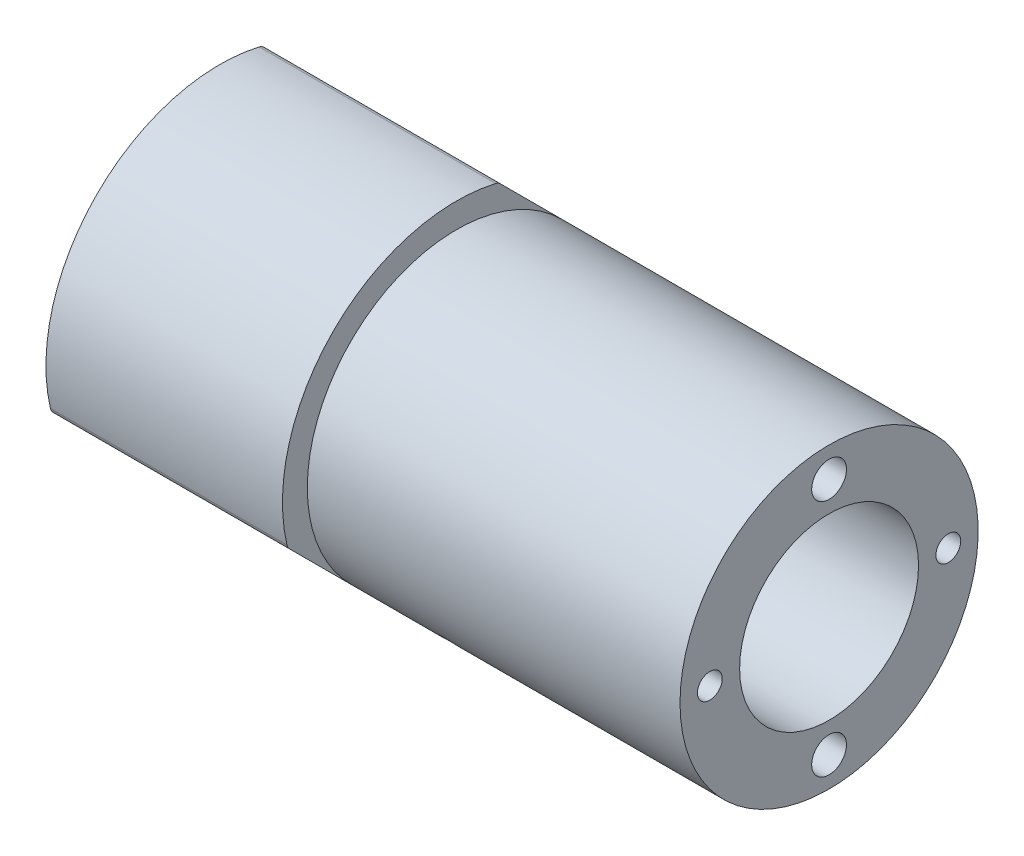
SolidWorks part; units mm, degrees
other "Markup1"
sketch "Sketch17" plane through (198.0015, -131.0823, 17.4914) normal (-0.589, 0.0933, 0.8027) x (0.8081, 0.0619, 0.5858)
sketch "Sketch19" plane through (198.0015, -131.0737, 17.5) normal (-0.589, 0.0933, 0.8027) x (0.8081, 0.0619, 0.5858)
material "AISI 304"
ref_plane "Front Plane" through (0, 0, 0) normal (0, 0, 1) x (1, 0, 0)
ref_plane "Top Plane" through (0, 0, 0) normal (0, 1, 0) x (1, 0, 0)
ref_plane "Right Plane" through (0, 0, 0) normal (1, 0, 0) x (0, 0, -1)
sketch "Sketch3" plane through (0, 0, 0) normal (0, 0, 1) x (1, 0, 0)
  line L0 (-58.5481, 189.9573) -> (284.033, 189.9573) construction
  line L2 (213.4012, -189.6279) -> (558.7345, -189.6279) construction
  line L4 (227.3705, -148.5737) -> (308.4812, -148.5737) construction
  line L25 (233.6593, -146.8737) -> (233.6593, -145.6737)
  line L26 (233.6593, -145.6737) -> (300.6593, -145.6737)
  line L27 (300.6593, -145.6737) -> (300.6593, -148.1737)
  line L28 (300.6593, -148.1737) -> (284.5593, -148.1737)
  line L29 (284.5593, -148.1737) -> (284.5593, -146.8713)
  line L30 (284.5593, -146.8713) -> (233.6593, -146.8737)
  line L31 (251.8003, -145.6737) -> (251.8003, -143.5284)
  line L32 (251.8003, -143.5284) -> (253.3698, -143.5284)
  line L33 (253.3698, -143.5284) -> (253.3698, -140.805)
  line L34 (253.3698, -140.805) -> (248.9846, -140.805)
  line L35 (248.9846, -140.805) -> (248.9846, -145.6737)
  line L36 (248.9846, -145.6737) -> (251.8003, -145.6737)
  line L38 (248.9846, -141.4136) -> (235.8861, -141.4136)
  line L39 (235.8861, -141.4136) -> (235.8861, -143.2479)
  line L40 (235.8861, -143.2479) -> (234.2244, -143.2479)
  line L41 (234.2244, -143.2479) -> (234.2244, -143.537)
  line L42 (234.2244, -143.537) -> (233.6702, -143.537)
  line L43 (233.6702, -143.537) -> (233.6702, -143.9524)
  line L44 (233.6702, -143.9524) -> (231.1317, -143.9524)
  line L45 (231.1317, -143.9524) -> (231.1317, -142.3308)
  line L46 (231.1317, -142.3308) -> (224.8078, -142.3308)
  line L47 (224.8078, -142.3308) -> (224.8078, -145.1987)
  line L48 (224.8078, -145.1987) -> (223.8385, -145.1987)
  line L49 (223.8385, -145.1987) -> (223.8385, -144.6096)
  line L50 (223.8385, -144.6096) -> (224.4112, -144.6096)
  line L51 (224.4112, -144.6096) -> (224.4112, -144.369)
  line L52 (224.4112, -144.369) -> (222.6328, -144.369)
  line L53 (222.6328, -144.369) -> (222.6328, -142.6667)
  line L54 (222.6328, -142.6667) -> (212.7719, -142.6667)
  line L55 (212.7719, -142.6667) -> (212.7719, -143.1416)
  line L56 (212.7719, -143.1416) -> (211.9894, -143.1416)
  line L57 (211.9894, -143.1416) -> (211.9894, -143.5179)
  line L58 (211.9894, -143.5179) -> (209.8233, -143.5179)
  line L59 (209.8233, -143.5179) -> (209.8233, -146.4993)
  line L60 (209.8233, -146.4993) -> (209.8233, -146.8823)
  line L61 (209.8233, -146.8823) -> (210.2598, -146.8823)
  line L62 (210.2598, -146.8823) -> (210.2598, -147.3433)
  line L63 (210.2598, -147.3433) -> (222.6328, -147.3433)
  line L64 (222.6328, -147.3433) -> (222.6328, -147.7892)
  line L65 (222.6328, -147.7892) -> (233.6593, -147.7892)
  line L66 (233.6593, -147.7892) -> (233.6593, -145.6737)
  line L67 (248.9846, -145.6737) -> (233.6593, -145.6737)
  line L68 (233.6593, -145.6737) -> (248.9846, -145.6737)
  line L69 (209.8233, -145.6737) -> (205.1515, -145.6737)
  line L70 (205.1515, -145.6737) -> (205.1515, -140.5737)
  line L71 (205.1515, -140.5737) -> (212.7719, -140.5737)
  line L72 (212.7719, -140.5737) -> (212.7719, -143.1416)
  line L73 (211.9894, -143.1416) -> (211.9894, -143.5179)
  line L74 (209.8233, -143.5179) -> (209.8233, -145.6737)
  line L75 (205.1515, -145.1987) -> (198.0015, -145.1987)
  line L83 (259.3015, -139.5737) -> (208.5515, -139.5737)
  line L84 (208.5515, -139.5737) -> (208.5515, -140.5737)
  line L85 (208.5515, -140.5737) -> (205.1515, -140.5737)
  line L86 (205.1515, -145.1987) -> (205.1515, -140.5737)
  line L87 (238.4273, -133.5737) -> (238.4273, -129.7144)
  line L88 (238.4273, -129.7144) -> (264.4415, -129.7144)
  line L89 (264.4415, -141.0573) -> (264.4415, -129.7144)
  line L90 (264.4415, -141.0573) -> (261.9375, -141.0573)
  line L91 (238.4273, -133.5737) -> (259.3015, -133.5737)
  line L92 (259.3015, -133.5737) -> (259.3015, -139.5737)
  line L93 (259.3015, -139.5737) -> (259.3015, -140.788)
  line L94 (259.3015, -140.788) -> (261.9375, -140.788)
  line L95 (250.6852, -139.5737) -> (250.6852, -140.805)
  line L96 (253.3698, -143.5284) -> (259.3015, -143.5284)
  line L97 (259.3015, -143.5284) -> (259.3015, -140.788)
  line L98 (259.3015, -143.5284) -> (302.0274, -143.5284)
  line L99 (302.0274, -143.5284) -> (302.0274, -145.1901)
  line L100 (302.0274, -145.1901) -> (304.5325, -145.1901)
  line L101 (304.5325, -145.1901) -> (304.5325, -141.0573)
  line L102 (304.5325, -141.0573) -> (264.4415, -141.0573)
  line L103 (238.4273, -133.5737) -> (221.8015, -133.5737)
  line L104 (161.2028, -147.3433) -> (161.2028, -146.4993)
  line L105 (161.2028, -146.4993) -> (209.8233, -146.4993)
  line L106 (209.8233, -146.8823) -> (210.2598, -146.8823)
  line L107 (210.2598, -147.3433) -> (222.6328, -147.3433)
  line L108 (210.2598, -147.3433) -> (161.2028, -147.3433)
  line L109 (209.8233, -146.4993) -> (209.8233, -146.8823)
  line L110 (209.8233, -146.8823) -> (210.2598, -146.8823)
  line L111 (210.2598, -146.8823) -> (210.2598, -147.3433)
  line L112 (261.9375, -141.0573) -> (261.9375, -140.788)
  line L114 (198.0015, -140.5561) -> (198.0015, -145.1987)
  line L115 (198.0015, -133.5737) -> (198.0015, -131.0737)
  line L116 (198.0015, -133.5737) -> (198.0015, -140.5561)
  line L117 (198.0015, -131.0737) -> (221.8015, -131.0737)
  line L118 (221.8015, -131.0737) -> (221.8015, -133.5737)
  dimension "D1" = 1.7
  dimension "D2" = 0.4
  dimension "D3" = 2.5
  dimension "D4" = 67
  dimension "D5" = 16.1
  dimension "D6" = 2.5
  dimension "D7" = 54.15
  dimension "D8" = 15
  dimension "D9" = 61.3
  dimension "D10" = 2.1446
  dimension "D11" = 6.75
  dimension "D12" = 17.5
  dimension "D13" = 8
  dimension "D14" = 9
  dimension "D15" = 37.5
  dimension "D16" = 50.75
revolve "Revolve1" add sketch "Sketch3" angle 360 about L4 region at (223.8128, -136.5584, 0)
ref_axis "Axis1" through (205.1515, -148.5737, 0) along (-1, 0, 0)
ref_plane "Plane1" through (0, -148.5737, 0) normal (0, 1, 0) x (1, 0, 0)
sketch "Sketch8" plane through (259.3015, 0, 0) normal (1, 0, 0) x (0, 0, -1)
  circle A1 centre (0, -136.5737) radius 1.75
  circle A3 centre (0, -160.5737) radius 1.75
  circle A4 centre (0, -148.5737) radius 12 construction
  point P9 (0, -148.5737)
  dimension "D1" = 24
  dimension "D2" = 3.5
  dimension "D3" = 3.5
  dimension "D4" = 0
extrude "Cut-Extrude1" cut sketch "Sketch8" against normal up to next
sketch "Sketch9" plane through (259.3015, 0, 0) normal (1, 0, 0) x (0, 0, -1)
  circle A0 centre (0, -148.5737) radius 12 construction
  dimension "D1" = 24
hole_wizard "Tap Drill for M3 Tap2" positions "Sketch11" profile "Sketch12" hole size "M3" standard "ISO"
sketch "Sketch11" plane through (259.3015, 0, 0) normal (1, 0, 0) x (0, 0, -1)
  circle A0 centre (0, -148.5737) radius 12 construction
  point P0 (-12, -148.5737)
  point P4 (12, -148.5737)
sketch "Sketch12" plane through (259.3015, -148.5737, 12) normal (0, 1, 0) x (0, 0, -1)
  line L0 (0, 0) -> (0, 6.7511)
  line L1 (0, 6.7511) -> (1.25, 6)
  line L2 (1.25, 6) -> (1.25, 0)
  line L5 (1.25, 0) -> (0, 0)
  line L10 (0, 6.7511) -> (-1.25, 6) construction
  line L11 (0, -6.35) -> (0, 107.95) construction
  dimension "Hole Dia." = 2.5
  dimension "Hole Depth" = 6
  dimension "Drill Angle" = 118
hole_wizard "Tap Drill for M6 Tap1" positions "Sketch15" profile "Sketch14" hole size "M6" standard "ISO"
sketch "Sketch15" plane through (198.0015, 0, 0) normal (-1, 0, 0) x (0, 0, 1)
  circle A1 centre (0, -148.5737) radius 12 construction
  point P8 (-12, -148.5737)
  point P10 (12, -148.5737)
  dimension "D1" = 24
sketch "Sketch14" plane through (198.0015, -148.5737, 12) normal (0, 1, 0) x (0, 0, 1)
  line L0 (0, 0) -> (0, 11.5022)
  line L1 (0, 11.5022) -> (2.5, 10)
  line L2 (2.5, 10) -> (2.5, 0)
  line L5 (2.5, 0) -> (0, 0)
  line L10 (0, 11.5022) -> (-2.5, 10) construction
  line L11 (0, -6.35) -> (0, 107.95) construction
  dimension "Hole Dia." = 5
  dimension "Hole Depth" = 10
  dimension "Drill Angle" = 118
sketch "Sketch16" plane through (198.0015, 0, 0) normal (-1, 0, 0) x (0, 0, 1)
  line L0 (0, -148.5737) -> (-10.6066, -137.9671) construction
  line L1 (-16.9804, -144.3409) -> (-4.2328, -131.5933)
  line L2 (-4.2328, -131.5933) -> (-6.3541, -129.472)
  line L3 (-16.9804, -144.3409) -> (-19.1017, -142.2196)
  line L4 (-19.1017, -142.2196) -> (-6.3541, -129.472)
  line L5 (-11.7138, -160.2875) -> (11.7138, -136.8599) construction
  line L6 (0, -148.5737) -> (-15, -148.5737) construction
  line L7 (4.2328, -165.5541) -> (6.3541, -167.6754)
  line L8 (4.2328, -165.5541) -> (16.9804, -152.8065)
  line L9 (16.9804, -152.8065) -> (19.1017, -154.9279)
  line L10 (6.3541, -167.6754) -> (19.1017, -154.9279)
  circle A0 centre (0, -148.5737) radius 15 construction
  circle A1 centre (0, -148.5737) radius 17.5 construction
  point P9 (-10.6066, -137.9671)
  point P14 (0, -148.5737)
  dimension "D1" = 90
  dimension "D2" = 45
extrude "Cut-Extrude2" cut sketch "Sketch16" against normal up to next
fillet "Fillet1" radius 1 4 edges at (209.9015, -165.5541, 4.2328) (209.9015, -152.8065, 16.9804) (209.9015, -144.3409, -16.9804) (209.9015, -131.5933, -4.2328)
sketch "Sketch18" plane through (0, -289.8444, -120.0575) normal (0, 0.7071, -0.7071) x (1, 0, 0)
  line L1 (221.8015, -199.7869) -> (221.8015, -184.7869) construction
  circle A1 centre (231.8015, -184.7869) radius 1
  dimension "D1" = 2
  dimension "D2" = 10
extrude "Cut-Extrude3" cut sketch "Sketch18" along normal up to next
equation "\"D3@Sketch8\"=\"D2@Sketch8\""
